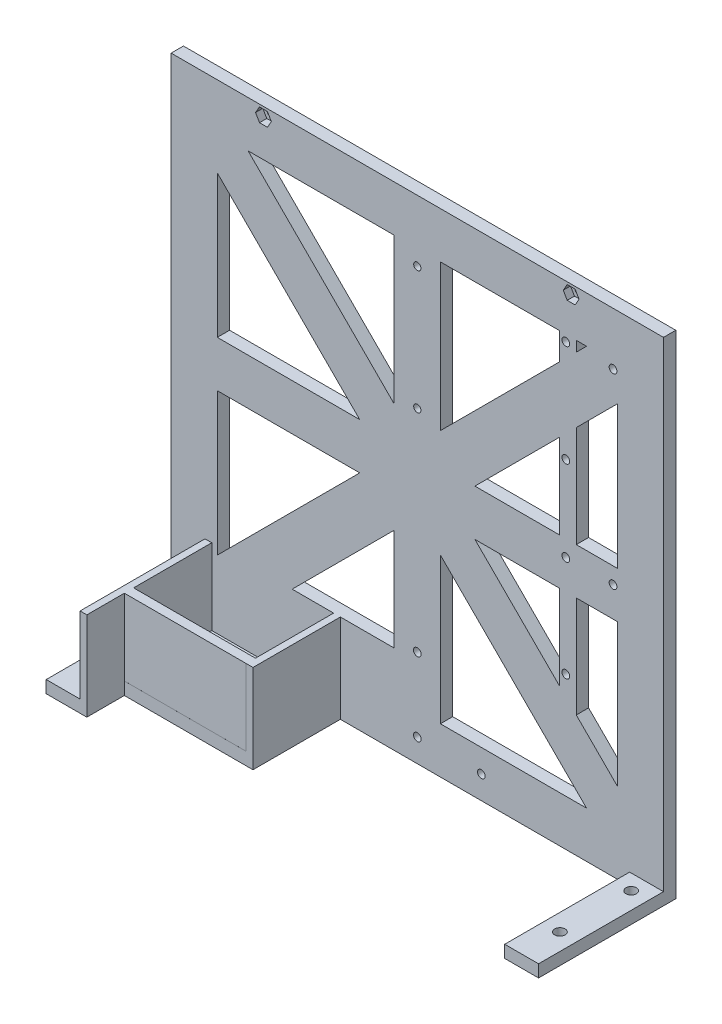
SolidWorks part; units mm, degrees
ref_plane "Front" through (0, 0, 0) normal (0, 0, 1) x (1, 0, 0)
ref_plane "Top" through (0, 0, 0) normal (0, 1, 0) x (1, 0, 0)
ref_plane "Right" through (0, 0, 0) normal (1, 0, 0) x (0, 0, -1)
sketch "Sketch1" plane through (0, 0, 0) normal (0, 0, 1) x (1, 0, 0)
  line L1 (-101.6, 101.6) -> (101.6, 101.6)
  line L2 (-101.6, 101.6) -> (-101.6, -101.6)
  line L3 (-101.6, -101.6) -> (101.6, -101.6)
  line L4 (101.6, 101.6) -> (101.6, -101.6)
  line L5 (-101.6, 101.6) -> (101.6, -101.6) construction
  line L6 (-101.6, -101.6) -> (101.6, 101.6) construction
  line L7 (0, -55) -> (0, 55) construction
  line L10 (-9.525, -22.8914) -> (-9.525, -65.024)
  line L17 (9.525, 22.225) -> (69.85, 82.55)
  line L18 (9.525, 82.55) -> (9.525, 22.225)
  line L19 (69.85, 82.55) -> (9.525, 82.55)
  line L23 (23.7658, 9.525) -> (82.55, 9.525)
  line L24 (23.7658, -9.525) -> (82.55, -9.525)
  line L25 (23.7658, 9.525) -> (82.55, 68.3092)
  line L26 (23.7658, -9.525) -> (82.55, -68.3092)
  line L27 (82.55, 9.525) -> (82.55, 68.3092)
  line L28 (82.55, -9.525) -> (82.55, -68.3092)
  line L29 (9.525, -22.225) -> (69.85, -82.55)
  line L30 (69.85, -82.55) -> (9.525, -82.55)
  line L31 (9.525, -82.55) -> (9.525, -22.225)
  line L32 (0, -101.6) -> (0, 101.6) construction
  line L36 (-82.55, -9.525) -> (-82.55, -68.3092)
  line L37 (-82.55, 9.525) -> (-82.55, 68.3092)
  line L38 (-23.7658, -9.525) -> (-82.55, -68.3092)
  line L39 (-23.7658, 9.525) -> (-82.55, 68.3092)
  line L40 (-23.7658, -9.525) -> (-82.55, -9.525)
  line L41 (-23.7658, 9.525) -> (-82.55, 9.525)
  line L42 (-69.85, 82.55) -> (-9.525, 82.55)
  line L43 (-9.525, 82.55) -> (-9.525, 22.225)
  line L44 (-9.525, 22.225) -> (-69.85, 82.55)
  line L45 (-9.525, -65.024) -> (-51.6576, -65.024)
  line L46 (-51.6576, -65.024) -> (-9.525, -22.8914)
  line L48 (58.7581, 87.2082) -> (65.6057, 87.2082)
  line L49 (58.7581, 87.2082) -> (58.7581, 4.2426)
  line L50 (58.7581, 4.2426) -> (65.6057, 4.2426)
  line L51 (65.6057, 87.2082) -> (65.6057, 4.2426)
  line L56 (58.7581, -5.8139) -> (65.6057, -5.8139)
  line L57 (58.7581, -5.8139) -> (58.7581, -58.6102)
  line L58 (58.7581, -58.6102) -> (65.6057, -58.6102)
  line L59 (65.6057, -5.8139) -> (65.6057, -58.6102)
  line L70 (90.1937, 58.9244) -> (90.1937, 51.0678)
  line L72 (0, 58.9244) -> (0, 51.0678)
  circle A0 centre (0, 76.2) radius 1.5
  circle A2 centre (0, 25.4) radius 1.5
  circle A3 centre (-63.5, 97.79) radius 1.5
  circle A4 centre (63.5, 97.79) radius 1.5
  point P0 (0, 0)
  dimension "D3" = 3
  dimension "D4" = 50.8
  dimension "D6" = 19.05
  dimension "D7" = 3
  dimension "D9" = 63.5
  dimension "D1" = 203.2
  dimension "D2" = 203.2
  dimension "D5" = 25.4
  dimension "D8" = 3.81
  dimension "D10" = 19.05
  dimension "D11" = 19.05
  dimension "D12" = 19.05
  dimension "D13" = 19.05
  dimension "D14" = 19.05
  dimension "D15" = 9.525
  dimension "D16" = 36.576
  dimension "D17" = 31.75
extrude "Boss-Extrude1" add sketch "Sketch1" along normal blind 5.08 contours L4 L1 L2 L3 L27 L23 L51 L50 L49 L25 L17 L18 L19 L48 L56 L59 L24 L28 L26 L58 L57 L45 L46 L10 L43 | L49 L48 L51 L50 | L57 L56 L59 L58 region at (-1.9817, -2.9175, 0)
sketch "Sketch2" plane through (0, 0, 5.08) normal (0, 0, 1) x (1, 0, 0)
  line L0 (-101.6, -101.6) -> (101.6, -101.6) construction
  line L2 (-101.6, -101.6) -> (-101.6, -96.52)
  line L5 (-9.525, -65.024) -> (-51.6576, -65.024) construction
  line L13 (-101.6, -101.6) -> (-31.75, -101.6)
  line L17 (-87.63, -65.024) -> (-84.836, -65.024)
  line L18 (-84.836, -96.4094) -> (-84.836, -65.024)
  line L23 (-84.836, -96.4094) -> (-34.544, -96.4094)
  line L24 (-101.6, -96.52) -> (-87.63, -96.52)
  line L25 (-87.63, -96.52) -> (-87.63, -65.024)
  line L28 (-34.544, -96.4094) -> (-34.544, -65.024)
  line L29 (-34.544, -65.024) -> (-31.75, -65.024)
  line L30 (-31.75, -65.024) -> (-31.75, -101.6)
  line L31 (101.6, -101.6) -> (87.63, -101.6)
  line L32 (101.6, -101.6) -> (101.6, -96.52)
  line L33 (101.6, -96.52) -> (87.63, -96.52)
  line L34 (87.63, -101.6) -> (87.63, -96.52)
  line M7 (101.6, -101.6) -> (101.6, 101.6)
  line M9 (-101.6, 101.6) -> (-101.6, -101.6)
  line M10 (-101.6, -101.6) -> (101.6, -101.6)
  dimension "D1" = 5.08
  dimension "D2" = 50.292
  dimension "D4" = 13.97
  dimension "D5" = 2.794
  dimension "D6" = 2.794
  dimension "D8" = 31.3854
extrude "Boss-Extrude2" add sketch "Sketch2" along normal blind 51.562 contours L23 L18 L17 L25 L24 M10 M9 | L34 L33 M10 M7 region at (94.615, -99.06, 5.08) region at (-100.8115, -99.06, 5.08)
sketch "Sketch3" plane through (0, -96.52, 0) normal (0, 1, 0) x (1, 0, 0)
  line L0 (-101.6, 0) -> (101.6, 0) construction
  line L2 (-87.63, -56.642) -> (-87.63, -5.08) construction
  line L4 (0, -55) -> (0, 55) construction
  line L5 (-101.6, -56.642) -> (-101.6, -5.08) construction
  circle A0 centre (-94.615, -11.43) radius 2.159
  circle A1 centre (94.615, -11.43) radius 2.159
  circle A2 centre (-94.615, -40.84) radius 2.159
  circle A3 centre (94.615, -40.84) radius 2.159
  dimension "D1" = 4.318
  dimension "D4" = 29.41
  dimension "D5" = 4.318
  dimension "D6" = 4.318
  dimension "D7" = 6.985
  dimension "D2" = 11.43
  dimension "D8" = 29.41
  dimension "D3" = 6.985
extrude "Cut-Extrude1" cut sketch "Sketch3" against normal up to next contours A0 | A1 | A3 | A2 | A2 | A3 region at (-94.615, -96.52, 11.43) region at (94.615, -96.52, 11.43) region at (-94.615, -96.52, 40.84) region at (94.615, -96.52, 40.84)
sketch "Sketch7" plane through (0, 0, 5.08) normal (0, 0, 1) x (1, 0, 0)
  line L1 (69.85, -82.55) -> (9.525, -82.55) construction
  circle A0 centre (0, -92.075) radius 1.5875
  circle A1 centre (0, -61.722) radius 1.5875
  circle A3 centre (26.416, -92.075) radius 1.5875
  dimension "D1" = 3.175
  dimension "D3" = 26.416
  dimension "D5" = 9.525
extrude "Cut-Extrude2" cut sketch "Sketch7" against normal up to next
sketch "Sketch11" plane through (0, 0, 5.08) normal (0, 0, 1) x (1, 0, 0)
  line L0 (0, -55) -> (0, 55) construction
  line L1 (-61.869, 94.965) -> (-60.238, 97.79)
  line L2 (-60.238, 97.79) -> (-61.869, 100.615)
  line L3 (-61.869, 100.615) -> (-65.131, 100.615)
  line L4 (-65.131, 100.615) -> (-66.762, 97.79)
  line L5 (-66.762, 97.79) -> (-65.131, 94.965)
  line L6 (-65.131, 94.965) -> (-61.869, 94.965)
  line L7 (65.131, 94.965) -> (61.869, 94.965)
  line L8 (66.762, 97.79) -> (65.131, 94.965)
  line L9 (65.131, 100.615) -> (66.762, 97.79)
  line L10 (61.869, 100.615) -> (65.131, 100.615)
  line L11 (60.238, 97.79) -> (61.869, 100.615)
  line L12 (61.869, 94.965) -> (60.238, 97.79)
  circle A0 centre (-63.5, 97.79) radius 1.5 construction
  circle A1 centre (-63.5, 97.79) radius 1.5
  circle A2 centre (-63.5, 97.79) radius 2.825 construction
  circle A3 centre (63.5, 97.79) radius 2.825 construction
  circle A4 centre (63.5, 97.79) radius 1.5
  dimension "D1" = 5.65
extrude "Cut-Extrude4" cut sketch "Sketch11" against normal blind 3 contours L5 L6 L1 L2 L3 L4 | L12 L7 L8 L9 L10 L11 region at (-63.5, 95.0513, 5.08) region at (63.5, 95.0513, 5.08)
sketch "Sketch12" plane through (-34.544, 0, 0) normal (-1, 0, 0) x (0, 0, 1)
  line L0 (56.642, -96.52) -> (5.08, -96.52) construction
  line L1 (41.148, -96.52) -> (37.338, -96.52)
  line L2 (41.148, -96.52) -> (41.148, -65.024)
  line L3 (41.148, -65.024) -> (37.338, -65.024)
  line L4 (37.338, -96.52) -> (37.338, -65.024)
  line L5 (56.642, -65.024) -> (5.08, -65.024) construction
  line L6 (5.08, 101.6) -> (5.08, -96.52) construction
  dimension "D1" = 3.81
  dimension "D2" = 32.258
extrude "Boss-Extrude3" add sketch "Sketch12" along normal up to next
sketch "Sketch14" plane through (-31.75, 0, 0) normal (1, 0, 0) x (0, 0, -1)
  line L0 (-56.642, -65.024) -> (-5.08, -65.024) construction
  line L1 (-56.642, -101.6) -> (-41.152, -101.6)
  line L2 (-56.642, -101.6) -> (-56.642, -65.024)
  line L3 (-56.642, -65.024) -> (-41.152, -65.024)
  line L4 (-41.152, -101.6) -> (-41.152, -65.024)
  dimension "D1" = 15.49
extrude "Cut-Extrude5" cut sketch "Sketch14" against normal up to surface (53.086 mm away) up to face at (-84.836, -80.7167, 48.895)
sketch "Sketch15" plane through (0, 0, 5.08) normal (0, 0, 1) x (1, 0, 0)
  line L0 (61.2852, -38.9377) -> (80.7852, -38.9377) construction
  line L1 (61.2852, 37.854) -> (80.7852, 37.854) construction
  line L2 (61.2852, 37.854) -> (61.2852, 79.854) construction
  line L3 (61.2852, 79.854) -> (80.7852, 79.854) construction
  line L4 (80.7852, 37.854) -> (80.7852, 79.854) construction
  line L5 (61.2852, -38.9377) -> (61.2852, 2.7864) construction
  line L6 (61.2852, 2.7864) -> (80.7852, 2.7864) construction
  line L7 (80.7852, -38.9377) -> (80.7852, 2.7864) construction
  circle A0 centre (61.2852, 79.854) radius 1.6
  circle A1 centre (80.7852, 79.854) radius 1.6
  circle A2 centre (80.7852, 37.854) radius 1.6
  circle A3 centre (61.2852, 37.854) radius 1.6
  circle A4 centre (61.2852, 2.7864) radius 1.6
  circle A5 centre (80.7852, 2.7864) radius 1.6
  circle A6 centre (80.7852, -38.9377) radius 1.6
  circle A7 centre (61.2852, -38.9377) radius 1.6
  dimension "D1" = 19.5
  dimension "D2" = 42
  dimension "D3" = 3.2
  dimension "D4" = 3.2
  dimension "D5" = 3.2
  dimension "D6" = 3.2
  dimension "D8" = 3.2
  dimension "D9" = 3.2
  dimension "D10" = 3.2
  dimension "D7" = 19.5
  dimension "D11" = 41.7241
extrude "Cut-Extrude6" cut sketch "Sketch15" against normal blind 10
sketch "Sketch16" plane through (0, 0, 0) normal (0, 0, -1) x (-1, 0, 0)
  line L1 (-1.5877, 73.45) -> (1.5877, 73.45)
  line L2 (1.5877, 73.45) -> (3.1754, 76.2)
  line L3 (3.1754, 76.2) -> (1.5877, 78.95)
  line L4 (1.5877, 78.95) -> (-1.5877, 78.95)
  line L5 (-1.5877, 78.95) -> (-3.1754, 76.2)
  line L6 (-3.1754, 76.2) -> (-1.5877, 73.45)
  line L7 (-62.8729, 77.104) -> (-59.6975, 77.104)
  line L8 (-59.6975, 77.104) -> (-58.1097, 79.854)
  line L9 (-58.1097, 79.854) -> (-59.6975, 82.604)
  line L10 (-59.6975, 82.604) -> (-62.8729, 82.604)
  line L11 (-62.8729, 82.604) -> (-64.4606, 79.854)
  line L12 (-64.4606, 79.854) -> (-62.8729, 77.104)
  line L13 (-82.3729, 77.104) -> (-79.1975, 77.104)
  line L14 (-79.1975, 77.104) -> (-77.6097, 79.854)
  line L15 (-77.6097, 79.854) -> (-79.1975, 82.604)
  line L16 (-79.1975, 82.604) -> (-82.3729, 82.604)
  line L17 (-82.3729, 82.604) -> (-83.9606, 79.854)
  line L18 (-83.9606, 79.854) -> (-82.3729, 77.104)
  line L19 (-62.8729, 35.104) -> (-59.6975, 35.104)
  line L20 (-59.6975, 35.104) -> (-58.1097, 37.854)
  line L21 (-58.1097, 37.854) -> (-59.6975, 40.604)
  line L22 (-59.6975, 40.604) -> (-62.8729, 40.604)
  line L23 (-62.8729, 40.604) -> (-64.4606, 37.854)
  line L24 (-64.4606, 37.854) -> (-62.8729, 35.104)
  line L25 (-3.1754, 25.4) -> (-1.5877, 22.65)
  line L26 (-1.5877, 22.65) -> (1.5877, 22.65)
  line L27 (1.5877, 22.65) -> (3.1754, 25.4)
  line L28 (3.1754, 25.4) -> (1.5877, 28.15)
  line L29 (1.5877, 28.15) -> (-1.5877, 28.15)
  line L30 (-1.5877, 28.15) -> (-3.1754, 25.4)
  line L31 (-64.4606, 2.7864) -> (-62.8729, 0.0364)
  line L32 (-62.8729, 0.0364) -> (-59.6975, 0.0364)
  line L33 (-59.6975, 0.0364) -> (-58.1097, 2.7864)
  line L34 (-58.1097, 2.7864) -> (-59.6975, 5.5364)
  line L35 (-59.6975, 5.5364) -> (-62.8729, 5.5364)
  line L36 (-62.8729, 5.5364) -> (-64.4606, 2.7864)
  line L37 (-83.9606, 2.7864) -> (-82.3729, 0.0364)
  line L38 (-82.3729, 0.0364) -> (-79.1975, 0.0364)
  line L39 (-79.1975, 0.0364) -> (-77.6097, 2.7864)
  line L40 (-77.6097, 2.7864) -> (-79.1975, 5.5364)
  line L41 (-79.1975, 5.5364) -> (-82.3729, 5.5364)
  line L42 (-82.3729, 5.5364) -> (-83.9606, 2.7864)
  line L43 (-64.4606, -38.9377) -> (-62.8729, -41.6877)
  line L44 (-62.8729, -41.6877) -> (-59.6975, -41.6877)
  line L45 (-59.6975, -41.6877) -> (-58.1097, -38.9377)
  line L46 (-58.1097, -38.9377) -> (-59.6975, -36.1877)
  line L47 (-59.6975, -36.1877) -> (-62.8729, -36.1877)
  line L48 (-62.8729, -36.1877) -> (-64.4606, -38.9377)
  line L49 (-3.1754, -61.722) -> (-1.5877, -64.472)
  line L50 (-1.5877, -64.472) -> (1.5877, -64.472)
  line L51 (1.5877, -64.472) -> (3.1754, -61.722)
  line L52 (3.1754, -61.722) -> (1.5877, -58.972)
  line L53 (1.5877, -58.972) -> (-1.5877, -58.972)
  line L54 (-1.5877, -58.972) -> (-3.1754, -61.722)
  line L55 (-3.1754, -92.075) -> (-1.5877, -94.825)
  line L56 (-1.5877, -94.825) -> (1.5877, -94.825)
  line L57 (1.5877, -94.825) -> (3.1754, -92.075)
  line L58 (3.1754, -92.075) -> (1.5877, -89.325)
  line L59 (1.5877, -89.325) -> (-1.5877, -89.325)
  line L60 (-1.5877, -89.325) -> (-3.1754, -92.075)
  line L61 (-29.5914, -92.075) -> (-28.0037, -94.825)
  line L62 (-28.0037, -94.825) -> (-24.8283, -94.825)
  line L63 (-24.8283, -94.825) -> (-23.2406, -92.075)
  line L64 (-23.2406, -92.075) -> (-24.8283, -89.325)
  line L65 (-24.8283, -89.325) -> (-28.0037, -89.325)
  line L66 (-28.0037, -89.325) -> (-29.5914, -92.075)
  circle A0 centre (0, 76.2) radius 2.75 construction
  circle A1 centre (-61.2852, 79.854) radius 2.75 construction
  circle A2 centre (-80.7852, 79.854) radius 2.75 construction
  circle A3 centre (-61.2852, 37.854) radius 2.75 construction
  circle A4 centre (0, 25.4) radius 2.75 construction
  circle A5 centre (-61.2852, 2.7864) radius 2.75 construction
  circle A6 centre (-80.7852, 2.7864) radius 2.75 construction
  circle A7 centre (-61.2852, -38.9377) radius 2.75 construction
  circle A8 centre (0, -61.722) radius 2.75 construction
  circle A9 centre (0, -92.075) radius 2.75 construction
  circle A10 centre (-26.416, -92.075) radius 2.75 construction
  dimension "D1" = 5.5
  dimension "D2" = 5.5
extrude "Cut-Extrude7" cut sketch "Sketch16" against normal blind 2.3
